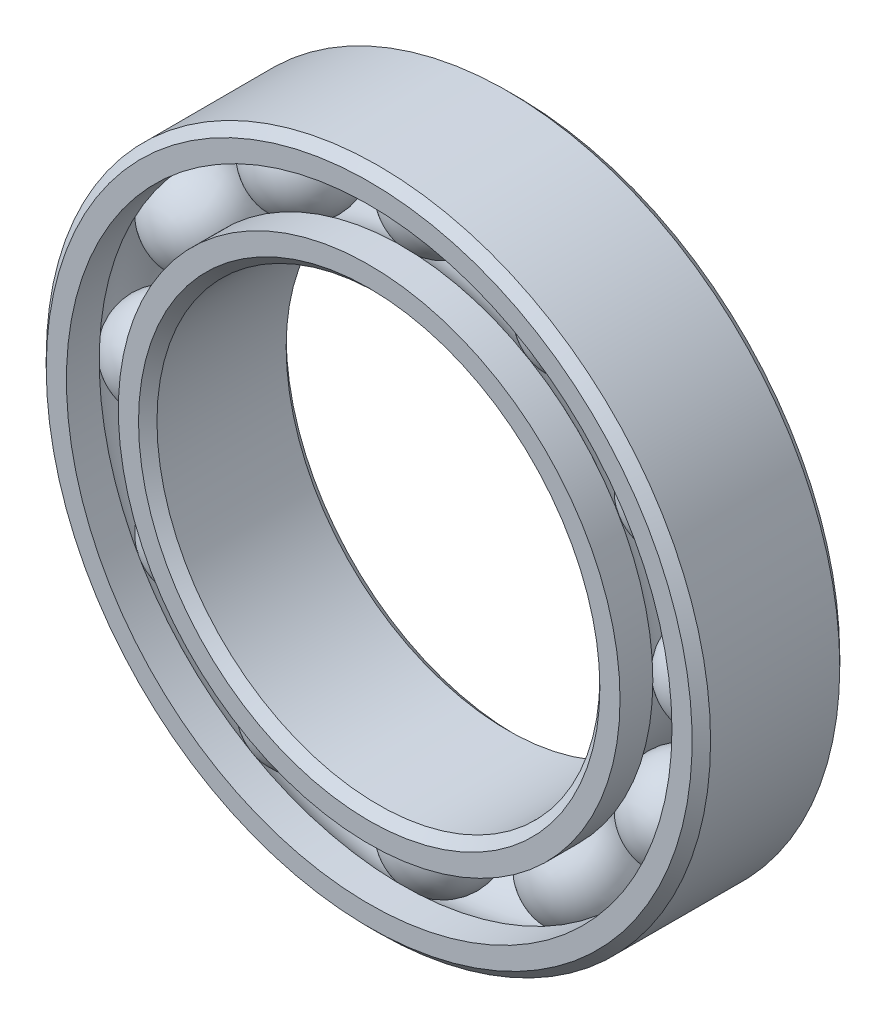
SolidWorks part; units mm, degrees
ref_plane "Front Plane" through (0, 0, 0) normal (0, 0, 1) x (1, 0, 0)
ref_plane "Top Plane" through (0, 0, 0) normal (0, 1, 0) x (1, 0, 0)
ref_plane "Right Plane" through (0, 0, 0) normal (1, 0, 0) x (0, 0, -1)
sketch "Sketch1" plane through (0, 0, 0) normal (1, 0, 0) x (0, 0, -1)
  line L0 (-2, 0) -> (2, 0) construction
  line L1 (0, 9) -> (0, -9) construction
  line L2 (1.75, 9) -> (-1.75, 9)
  line L3 (-1.75, 9) -> (-2, 8.75)
  line L4 (-2, 8.75) -> (-2, 8.2033)
  line L5 (-2, 8.2033) -> (-1.1111, 8.2033)
  line L6 (2, 8.2033) -> (1.1111, 8.2033)
  line L7 (2, 8.75) -> (2, 8.2033)
  line L8 (1.75, 9) -> (2, 8.75)
  line L9 (0, 9) -> (0, 7.5) construction
  line L10 (0, 7.5) -> (0, 6) construction
  arc A0 (-1.1111, 8.2033) -> (1.1111, 8.2033) centre (0, 7.5) cw
  point P14 (0, 6)
  dimension "Width" = 4
  dimension "OD" = 18
  dimension "D1" = 45
  dimension "D2" = 0.25
  dimension "Shaft Dia" = 12
  dimension "D3" = 2.2222
  dimension "D4" = 0.7033
revolve "Revolve1" add sketch "Sketch1" angle 360 about L0
sketch "Sketch3" plane through (0, 0, 0) normal (1, 0, 0) x (0, 0, -1)
  line L0 (-2, 6.7967) -> (-1.1111, 6.7967)
  line L1 (0, 9) -> (0, -9) construction
  line L2 (-2, 8.75) -> (-2, 8.2033) construction
  line L3 (-2, 6.7967) -> (-2, 6.25)
  line L4 (-1.75, 9) -> (-2, 8.75) construction
  line L5 (-2, 6.25) -> (-1.75, 6)
  line L6 (-1.75, 6) -> (1.75, 6)
  line L7 (1.75, 9) -> (1.75, -9) construction
  line L8 (1.75, 6) -> (2, 6.25)
  line L9 (2, -8.75) -> (2, 8.75) construction
  line L10 (2, 6.25) -> (2, 6.7967)
  line L11 (2, 6.7967) -> (1.1111, 6.7967)
  line L13 (1.75, 9) -> (2, 8.75) construction
  arc A0 (1.1111, 8.2033) -> (-1.1111, 8.2033) centre (0, 7.5) ccw construction
  arc A1 (1.1111, 6.7967) -> (-1.1111, 6.7967) centre (0, 7.5) cw
revolve "Revolve3" add sketch "Sketch3" angle 360 about L0
sketch "Sketch4" plane through (0, 0, 0) normal (1, 0, 0) x (0, 0, -1)
  line L0 (-1.315, 7.5) -> (1.315, 7.5)
  arc A2 (-1.315, 7.5) -> (1.315, 7.5) centre (0, 7.5) cw
  arc A3 (1.1111, 8.2033) -> (-1.1111, 8.2033) centre (0, 7.5) ccw construction
revolve "Revolve4" add sketch "Sketch4" angle 360 about L0
ref_axis "Axis1" through (0, 0, -2) along (0, 0, 1)
pattern_circular "CirPattern1" count 12 every 30 about axis through (0, 0, -2) along (0, 0, 1) of bodies 104
sketch "Sketch5" plane through (0, 0, 0) normal (1, 0, 0) x (0, 0, -1)
  line L0 (-2, 8.2033) -> (-1.1111, 8.2033) construction
  line L1 (-1.875, 8.2033) -> (-1.315, 8.2033)
  line L2 (-1.875, 8.2033) -> (-1.875, 6.7967)
  line L3 (-1.875, 6.7967) -> (-1.315, 6.7967)
  line L4 (-1.315, 8.2033) -> (-1.315, 6.7967)
  line L5 (-2, 6.7967) -> (-1.1111, 6.7967) construction
  line L6 (2, 8.2033) -> (1.1111, 8.2033) construction
  line L7 (1.875, 8.2033) -> (1.315, 8.2033)
  line L8 (1.875, 8.2033) -> (1.875, 6.7967)
  line L9 (1.875, 6.7967) -> (1.315, 6.7967)
  line L10 (1.315, 8.2033) -> (1.315, 6.7967)
  line L11 (2, 6.7967) -> (1.1111, 6.7967) construction
  line L12 (-1.75, 9) -> (-2, 8.75) construction
  point P18 (-1.875, 8.875)
equation "\"D2@Sketch1\" = \"Width@Sketch1\"*.05"
equation "\"D3@Sketch1\" = \"Width@Sketch1\"/2.25"
equation "\"D4@Sketch1\" = (((\"OD@Sketch1\"-\"Width@Sketch1\")/2)/3.25)/3.5"
equation "\"D2@CirPattern1\" = 360/\"Balls@CirPattern1\""
